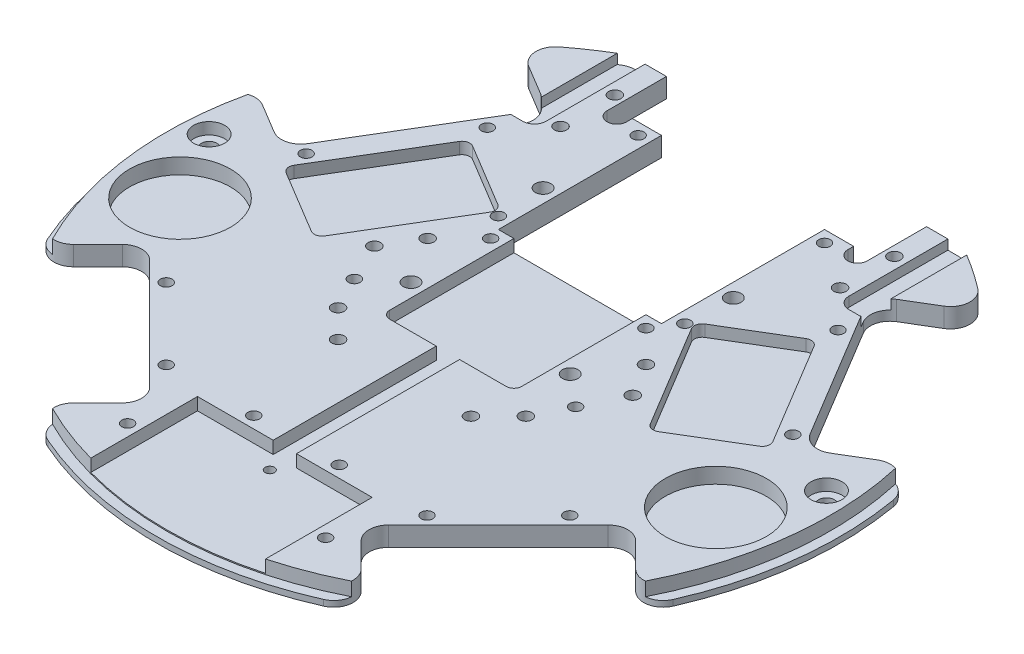
SolidWorks part; units mm, degrees
material "7079 Alloy"
ref_plane "Front" through (0, 0, 0) normal (0, 0, 1) x (1, 0, 0)
ref_plane "Top" through (0, 0, 0) normal (0, 1, 0) x (1, 0, 0)
ref_plane "Right" through (0, 0, 0) normal (1, 0, 0) x (0, 0, -1)
sketch "Sketch1" plane through (0, 0, 0) normal (0, 1, 0) x (1, 0, 0)
  line L0 (0, 0) -> (88, 0)
  line L1 (0, 88) -> (0, 0)
  line L2 (-88, 0) -> (0, 0)
  line L3 (0, -88) -> (0, 0)
  line L4 (0, 0) -> (62.2254, -62.2254)
  line L5 (0, 0) -> (-62.2254, -62.2254)
  line L6 (0, 0) -> (75.4307, 45.3234)
  line L7 (0, 0) -> (-75.4307, 45.3234)
  line L8 (59.4468, 64.8851) -> (41.5542, 54.1341)
  line L9 (41.5542, 54.1341) -> (67.3061, 11.2757)
  line L10 (67.3061, 11.2757) -> (85.1987, 22.0267)
  line L11 (77.3392, -41.9839) -> (62.579, -27.2236)
  line L12 (62.579, -27.2236) -> (27.2236, -62.579)
  line L13 (27.2236, -62.579) -> (41.9839, -77.3392)
  line L14 (-41.9839, -77.3392) -> (-27.2236, -62.579)
  line L15 (-27.2236, -62.579) -> (-62.579, -27.2236)
  line L16 (-62.579, -27.2236) -> (-77.3392, -41.9839)
  line L17 (-85.1987, 22.0267) -> (-67.3061, 11.2757)
  line L18 (-67.3061, 11.2757) -> (-41.5542, 54.1341)
  line L19 (-41.5542, 54.1341) -> (-59.4468, 64.8851)
  line L20 (-59.4468, 64.8851) -> (7.3885, 64.8851)
  line L21 (7.3885, 64.8851) -> (59.4468, 64.8851)
  line L22 (-41.5542, 54.1341) -> (0, 54.1341)
  line L23 (0, 54.1341) -> (41.5542, 54.1341)
  line L24 (41.5542, 54.1341) -> (41.5542, 77.5709)
  line L25 (-41.5542, 77.5709) -> (0, 77.5709)
  line L26 (-41.5542, 77.5709) -> (-41.5542, 54.1341)
  line L27 (0, 77.5709) -> (41.5542, 77.5709)
  circle A0 centre (0, 0) radius 88
  dimension "D1" = 176
  dimension "D2" = 31
  dimension "D3" = 31
  dimension "D4" = 45
  dimension "D5" = 24.5
  dimension "D6" = 24.5
  dimension "D7" = 24.5
  dimension "D8" = 24.5
  dimension "D9" = 25
  dimension "D10" = 25
  dimension "D11" = 25
  dimension "D12" = 25
  dimension "D13" = 25
  dimension "D14" = 25
  dimension "D15" = 25
  dimension "D16" = 25
sketch "Sketch2" plane through (0, 0, 0) normal (0, 1, 0) x (1, 0, 0)
  line L0 (85.1987, 22.0267) -> (67.3061, 11.2757)
  line L1 (67.3061, 11.2757) -> (41.5542, 54.1341)
  line L2 (77.3392, -41.9839) -> (62.579, -27.2236)
  line L3 (62.579, -27.2236) -> (27.2236, -62.579)
  line L4 (27.2236, -62.579) -> (41.9839, -77.3392)
  line L5 (-41.9839, -77.3392) -> (-27.2236, -62.579)
  line L6 (-27.2236, -62.579) -> (-62.579, -27.2236)
  line L7 (-62.579, -27.2236) -> (-77.3392, -41.9839)
  line L8 (-85.1987, 22.0267) -> (-67.3061, 11.2757)
  line L9 (-67.3061, 11.2757) -> (-41.5542, 54.1341)
  line L10 (-43, 76.7789) -> (43, 76.7789)
  line L15 (-41.5542, 54.1341) -> (-59.4468, 64.8851)
  line L16 (0, 0) -> (0, 111.6496) construction
  line L17 (41.5542, 54.1341) -> (59.4468, 64.8851)
  line L18 (-43, 76.7789) -> (43, 76.7789) construction
  arc A0 (85.1987, 22.0267) -> (77.3392, -41.9839) centre (0, 0) cw
  arc A1 (41.9839, -77.3392) -> (-41.9839, -77.3392) centre (0, 0) cw
  arc A2 (-77.3392, -41.9839) -> (-85.1987, 22.0267) centre (0, 0) cw
  arc A3 (-43, 76.7789) -> (-59.4468, 64.8851) centre (0, 0) ccw
  arc A4 (59.4468, 64.8851) -> (43, 76.7789) centre (0, 0) ccw
  dimension "D2" = 86
extrude "Extrude1" add sketch "Sketch2" against normal blind 5
sketch "Sketch3" plane through (0, 0, 0) normal (0, 1, 0) x (1, 0, 0)
  line L0 (-21, 76.7789) -> (-21, 21)
  line L1 (-21, 21) -> (21, 21)
  line L2 (21, 21) -> (21, 76.7789)
  line L3 (43, 76.7789) -> (-43, 76.7789) construction
  line L5 (-21, 76.7789) -> (21, 76.7789)
  dimension "D1" = 21
  dimension "D2" = 21
  dimension "D3" = 21
extrude "Extrude2" cut sketch "Sketch3" against normal up to surface (5 mm away) up to face at (0, -5, -1.5971)
sketch "Sketch4" plane through (0, 0, 0) normal (0, 1, 0) x (-1, 0, 0)
  line L0 (17, 13) -> (17, -27)
  line L2 (17, 13) -> (-17, 13)
  line L3 (17, -27) -> (-17, -27)
  line L4 (-17, -27) -> (-17, 13)
  line L5 (21, -21) -> (-21, -21) construction
  dimension "D1" = 34
  dimension "D2" = 17
  dimension "D3" = 34
  dimension "D4" = 40
extrude "Extrude3" cut sketch "Sketch4" against normal blind 3.2
sketch "Sketch5" plane through (0, 0, 0) normal (0, 1, 0) x (1, 0, 0)
  line L0 (42.9633, -4.5175) -> (62.6781, 7.3283)
  line L1 (62.6781, 7.3283) -> (44.6518, 37.3292)
  line L2 (44.6518, 37.3292) -> (24.9369, 25.4833)
  line L3 (24.9369, 25.4833) -> (42.9633, -4.5175)
  line L5 (67.3061, 11.2757) -> (41.5542, 54.1341) construction
  line L6 (85.1987, 22.0267) -> (67.3061, 11.2757) construction
  dimension "D1" = 6
  dimension "D2" = 35
  dimension "D3" = 23
  dimension "D4" = 1
extrude "Extrude4" cut sketch "Sketch5" against normal blind 3
mirror "Mirror1" about plane through (0, 0, 0) normal (1, 0, 0) of "Extrude4"
sketch "Sketch6" plane through (0, 0, 0) normal (0, 1, 0) x (1, 0, 0)
  line L0 (0, 0) -> (75.4307, 45.3234) construction
  line L1 (41.5542, 54.1341) -> (67.3061, 11.2757) construction
  line L2 (62.579, -27.2236) -> (27.2236, -62.579) construction
  line L3 (0, 0) -> (62.2254, -62.2254) construction
  circle A0 centre (45.1631, 42.303) radius 1.5
  circle A1 centre (62.6744, 13.1593) radius 1.5
  circle A2 centre (51.9723, -33.5876) radius 1.5
  circle A3 centre (33.5876, -51.9723) radius 1.5
  dimension "D1" = 3
  dimension "D2" = 3
  dimension "D3" = 3
  dimension "D4" = 3
  dimension "D6" = 3
  dimension "D8" = 3
  dimension "D9" = 3
  dimension "D10" = 13
  dimension "D11" = 13
  dimension "D12" = 3
  dimension "D5" = 13
  dimension "D7" = 21
extrude "Extrude5" cut sketch "Sketch6" against normal up to surface (5 mm away) up to face at (0, -5, -10.1957)
mirror "Mirror2" about plane through (0, 0, 0) normal (1, 0, 0) of "Extrude5"
sketch "Sketch7" plane through (0, 0, 0) normal (0, 1, 0) x (-1, 0, 0)
  line L1 (-21, -21) -> (-21, -76.7789) construction
  line L2 (-17, -21) -> (-21, -21) construction
  circle A0 centre (-24, -60) radius 1.5
  circle A1 centre (-24, -24) radius 1.5
  dimension "D2" = 3
  dimension "D3" = 3
  dimension "D4" = 3
  dimension "D5" = 3
  dimension "D6" = 3
  dimension "D1" = 36
extrude "Extrude6" cut sketch "Sketch7" against normal up to surface (5 mm away) up to face at (-51.9723, -5, 32.0876)
mirror "Mirror3" about plane through (0, 0, 0) normal (1, 0, 0) of "Extrude6"
sketch "Sketch8" plane through (0, 0, 0) normal (0, 1, 0) x (1, 0, 0)
  line L0 (33.5, 68.7344) -> (33.5, 63)
  line L6 (33.5, 63) -> (21, 63)
  line L7 (21, 21) -> (21, 76.7789) construction
  line L8 (21, 63) -> (21, 76.7789)
  line L9 (21, 76.7789) -> (33.5, 76.7789)
  line L10 (43, 76.7789) -> (21, 76.7789) construction
  line L11 (33.5, 76.7789) -> (33.5, 68.7344)
  circle A0 centre (24, 60) radius 1.5 construction
  dimension "D4" = 3
extrude "Extrude7" cut sketch "Sketch8" against normal up to surface (5 mm away) up to face at (-24, -5, -61.5)
mirror "Mirror4" about plane through (0, 0, 0) normal (1, 0, 0) of "Extrude7"
sketch "Sketch9" plane through (0, 0, 0) normal (0, 1, 0) x (1, 0, 0)
  line L5 (33.5, 63) -> (33.5, 76.7789) construction
  circle A0 centre (36, 66) radius 1.6
  circle A1 centre (36, 52) radius 1.6
  dimension "D1" = 3.2
  dimension "D2" = 3.2
  dimension "D3" = 52
  dimension "D4" = 66
  dimension "D5" = 2.5
extrude "Extrude8" cut sketch "Sketch9" against normal up to surface (5 mm away) up to face at (-24, -5, -61.5)
mirror "Mirror5" about plane through (0, 0, 0) normal (1, 0, 0) of "Extrude8"
fillet "Fillet2" radius 2 10 edges at (-17, -1.6, 13) (17, -1.6, 13) (-42.9633, -1.5, 4.5175) (-24.9369, -1.5, -25.4833) (-44.6518, -1.5, -37.3292) (-62.6781, -1.5, -7.3283) (42.9633, -1.5, 4.5175) (24.9369, -1.5, -25.4833) (44.6518, -1.5, -37.3292) (62.6781, -1.5, -7.3283)
fillet "Fillet3" radius 5 16 edges at (59.4468, -2.5, -64.8851) (41.5542, -2.5, -54.1341) (67.3061, -2.5, -11.2757) (85.1987, -2.5, -22.0267) (77.3392, -2.5, 41.9839) (62.579, -2.5, 27.2236) (27.2236, -2.5, 62.579) (41.9839, -2.5, 77.3392) (-27.2236, -2.5, 62.579) (-41.9839, -2.5, 77.3392) (-62.579, -2.5, 27.2236) (-77.3392, -2.5, 41.9839) (-85.1987, -2.5, -22.0267) (-67.3061, -2.5, -11.2757) (-41.5542, -2.5, -54.1341) (-59.4468, -2.5, -64.8851)
fillet "Fillet4" radius 5 2 edges at (43, -2.5, -76.7789) (-43, -2.5, -76.7789)
sketch "Sketch11" plane through (0, 0, 0) normal (0, 1, 0) x (1, 0, 0)
  line L3 (-21, 21) -> (-21, 63) construction
  line L4 (21, 21) -> (21, 63) construction
  circle A2 centre (24.5, 36) radius 2
  circle A3 centre (-24.5, 36) radius 2
  dimension "D7" = 4
  dimension "D8" = 4
  dimension "D9" = 3.5
  dimension "D10" = 3.5
extrude "Extrude10" cut sketch "Sketch11" against normal up to surface (5 mm away) up to face at (-36, -5, -67.6)
sketch "Sketch14" plane through (0, 0, 0) normal (0, 1, 0) x (1, 0, 0)
  line L3 (17.112, -24.1831) -> (24.1831, -17.112) construction
  line L4 (33.9018, -69.2571) -> (69.2571, -33.9018) construction
  line L8 (37.0444, -72.3997) -> (30.7591, -66.1145) construction
  line L9 (66.1145, -30.7591) -> (72.3997, -37.0444) construction
  line L10 (62.6744, 13.1593) -> (45.1631, 42.303) construction
  line L11 (49.6495, 58.9983) -> (75.4014, 16.1399) construction
  line L12 (45.84, 56.7093) -> (53.4591, 61.2873) construction
  line L13 (79.211, 18.4289) -> (71.5919, 13.8509) construction
  line L14 (33.5876, -51.9723) -> (51.9723, -33.5876) construction
  circle A2 centre (24.1831, -17.112) radius 1.6
  circle A3 centre (17.112, -24.1831) radius 1.6
  circle A4 centre (28.1195, 9.8961) radius 1.6
  circle A5 centre (33.2699, 1.3244) radius 1.6
  point P28 (20.6475, -20.6475)
  dimension "D3" = 3.2
  dimension "D4" = 31.3
  dimension "D7" = 31.3
  dimension "D9" = 3.2
  dimension "D10" = 31.3
  dimension "D12" = 10
  dimension "D8" = 3.2
  dimension "D14" = 3.2
  dimension "D2" = 10
  dimension "D5" = 31.3
  dimension "D6" = 19
  dimension "D13" = 25
sketch "Sketch15" plane through (0, 0, 0) normal (0, 1, 0) x (1, 0, 0)
  circle A0 centre (69, -13) radius 13
  dimension "D1" = 26
  dimension "D2" = 13
  dimension "D3" = 69
extrude "Extrude13" cut sketch "Sketch15" against normal blind 4
mirror "Mirror7" about plane through (0, 0, 0) normal (1, 0, 0) of "Extrude13"
sketch "Sketch16" plane through (0, 0, 0) normal (0, 1, 0) x (1, 0, 0)
  line L1 (-22.5, -55) -> (22.5, -55)
  line L2 (-22.5, -55) -> (-22.5, -95)
  line L3 (-22.5, -95) -> (22.5, -95)
  line L4 (22.5, -55) -> (22.5, -95)
  dimension "D1" = 22.5
  dimension "D2" = 22.5
  dimension "D3" = 55
  dimension "D4" = 40
extrude "Extrude14" cut sketch "Sketch16" against normal blind 3.2
sketch "Sketch17" plane through (0, 0, 0) normal (0, 1, 0) x (1, 0, 0)
  line L0 (22.5, -85.075) -> (22.5, -55) construction
  line L1 (-22.5, -55) -> (-22.5, -85.075) construction
  circle A0 centre (25.5, -70) radius 1.5
  circle A1 centre (-25.5, -70) radius 1.5
  dimension "D1" = 3
  dimension "D2" = 3
  dimension "D3" = 3
  dimension "D4" = 3
  dimension "D5" = 70
extrude "Extrude16" cut sketch "Sketch17" against normal up to surface (5 mm away) up to face at (-24.5, -5, -38)
sketch "Sketch18" plane through (0, 0, 0) normal (0, 1, 0) x (-1, 0, 0)
  line L0 (-22.5, 55) -> (22.5, 55) construction
  line L1 (-22.5, 55) -> (22.5, 55) construction
  circle A0 centre (-11, 52) radius 1.5
  circle A1 centre (11, 52) radius 1.5
  dimension "D1" = 3
  dimension "D2" = 3
  dimension "D3" = 3
  dimension "D4" = 3
  dimension "D5" = 11
  dimension "D6" = 11
extrude "Extrude17" cut sketch "Sketch18" against normal up to surface (5 mm away) up to face at (-25.5, -5, 68.5)
sketch "Sketch20" plane through (0, 0, 0) normal (0, 1, 0) x (1, 0, 0)
  circle A0 centre (20.5, -2) radius 2
  circle A1 centre (-20.5, -2) radius 2
  dimension "D1" = 4
  dimension "D2" = 4
  dimension "D3" = 20.5
  dimension "D4" = 20.5
  dimension "D5" = 2
  dimension "D6" = 2
extrude "Extrude19" cut sketch "Sketch20" against normal up to surface (5 mm away) up to face at (-11, -5, 50.5)
sketch "Sketch27" plane through (0, 0, 0) normal (0, 1, 0) x (1, 0, 0)
  line L1 (17, 21) -> (21, 21) construction
  line L2 (17, -11) -> (17, 21) construction
  line L3 (-17, 21) -> (-17, -11) construction
  circle A0 centre (20, 18) radius 1.5
  circle A1 centre (-20, 18) radius 1.5
  dimension "D1" = 3
  dimension "D2" = 3
  dimension "D4" = 3
  dimension "D3" = 3
  dimension "D5" = 3
extrude "Extrude26" cut sketch "Sketch27" against normal up to surface (5 mm away) up to face at (-20.5, -5, 0)
sketch "Sketch28" plane through (0, 0, 0) normal (0, 1, 0) x (1, 0, 0)
  circle A0 centre (28.5, -8.6) radius 1.5
  circle A1 centre (11, -52) radius 1.5 construction
  circle A2 centre (-28.5, -8.6) radius 1.5
  circle A3 centre (-11, -52) radius 1.5 construction
  dimension "D2" = 17.5
  dimension "D3" = 3
  dimension "D5" = 3
  dimension "D1" = 43.4
  dimension "D4" = 17.5
extrude "Extrude27" cut sketch "Sketch28" against normal up to surface (5 mm away) up to face at (-20, -5, -19.5)
sketch "Sketch29" plane through (0, 0, 0) normal (0, 1, 0) x (1, 0, 0)
  circle A0 centre (-79.5, 5) radius 4
  circle A1 centre (79.5, 5) radius 4
  dimension "D2" = 79.5
  dimension "D4" = 8
  dimension "D5" = 8
  dimension "D1" = 5
  dimension "D3" = 79.5
extrude "Extrude28" cut sketch "Sketch29" against normal blind 3
sketch "Sketch30" plane through (0, -3, 0) normal (0, 1, 0) x (1, 0, 0)
  circle A0 centre (79.5, 5) radius 2
  circle A1 centre (-79.5, 5) radius 2
  dimension "D1" = 4
  dimension "D2" = 4
extrude "Extrude29" cut sketch "Sketch30" against normal up to surface (2 mm away) up to face at (-28.5, -5, 7.1)
extrude "Extrude30" cut sketch "Sketch14" against normal up to surface (5 mm away) up to face at (-79.5, -5, -7)
mirror "Mirror9" about plane through (0, 0, 0) normal (1, 0, 0) of "Extrude30"
sketch "Sketch31" plane through (0, 0, 0) normal (0, 1, 0) x (1, 0, 0)
  line L0 (-74.1867, 42.5039) -> (-76.3559, 43.7467)
  line L2 (74.1867, 42.5039) -> (76.3559, 43.7467)
  arc A0 (-74.1867, 42.5039) -> (74.1867, 42.5039) centre (0, 0) ccw
  arc A1 (-76.3559, 43.7467) -> (76.3559, 43.7467) centre (0, 0) ccw
  dimension "D1" = 171
extrude "Cut-Extrude1" cut sketch "Sketch31" against normal blind 3.5
sketch "Sketch33" plane through (0, 0, 0) normal (0, 1, 0) x (1, 0, 0)
  line L0 (-39, 76.7789) -> (-45, 76.7789)
  line L3 (-33.5, 76.7789) -> (-41.6748, 76.7789) construction
  line L4 (-45, 76.7789) -> (-45, 48.2789)
  line L9 (-45, 48.2789) -> (-39, 48.2789)
  line L10 (-39, 48.2789) -> (-39, 76.7789)
  line L11 (0, 0) -> (0, 104.2822) construction
  line L12 (39, 48.2789) -> (39, 76.7789)
  line L13 (45, 48.2789) -> (39, 48.2789)
  line L14 (45, 76.7789) -> (45, 48.2789)
  line L15 (39, 76.7789) -> (45, 76.7789)
  dimension "D1" = 5.5
  dimension "D2" = 6
  dimension "D3" = 28.5
extrude "Cut-Extrude3" cut sketch "Sketch33" against normal blind 2.5
fillet "Fillet5" radius 3 2 edges at (39, -1.25, -48.2789) (-39, -1.25, -48.2789)
sketch "Sketch34" plane through (0, 0, 0) normal (0, 1, 0) x (1, 0, 0)
  line L0 (-33.5, 63) -> (-33.5, 59)
  line L1 (-33.5, 59) -> (-28.5, 59)
  line L2 (-28.5, 59) -> (-28.5, 63)
  line L4 (-21, 63) -> (-33.5, 63) construction
  line L5 (-28.5, 63) -> (-33.5, 63)
  line L6 (0, 0) -> (0, 90.7879) construction
  line L7 (28.5, 63) -> (33.5, 63)
  line L8 (28.5, 59) -> (28.5, 63)
  line L9 (33.5, 59) -> (28.5, 59)
  line L10 (33.5, 63) -> (33.5, 59)
  dimension "D1" = 4
  dimension "D2" = 5
extrude "Cut-Extrude4" cut sketch "Sketch34" against normal blind 10
fillet "Fillet6" radius 2.5 4 edges at (28.5, -2.5, -59) (33.5, -2.5, -59) (-28.5, -2.5, -59) (-33.5, -2.5, -59)
sketch "Sketch35" plane through (0, 0, 0) normal (0, 1, 0) x (1, 0, 0)
  line L0 (-3, -13) -> (-3, -55)
  line L1 (-15, -13) -> (15, -13) construction
  line L2 (22.5, -55) -> (-22.5, -55) construction
  line L3 (3, -13) -> (3, -55)
  line L4 (-15, -13) -> (15, -13) construction
  line L5 (22.5, -55) -> (-22.5, -55) construction
  line L6 (-3, -13) -> (3, -13)
  line L7 (-3, -55) -> (3, -55)
  line L8 (17, -11) -> (17, 21) construction
  dimension "D1" = 6
  dimension "D2" = 14
extrude "Cut-Extrude5" cut sketch "Sketch35" against normal blind 3.2
sketch "Sketch36" plane through (0, -3.2, 0) normal (0, 1, 0) x (1, 0, 0)
  circle A0 centre (0, -58.8697) radius 1.2
extrude "Cut-Extrude6" cut sketch "Sketch36" against normal blind 3
